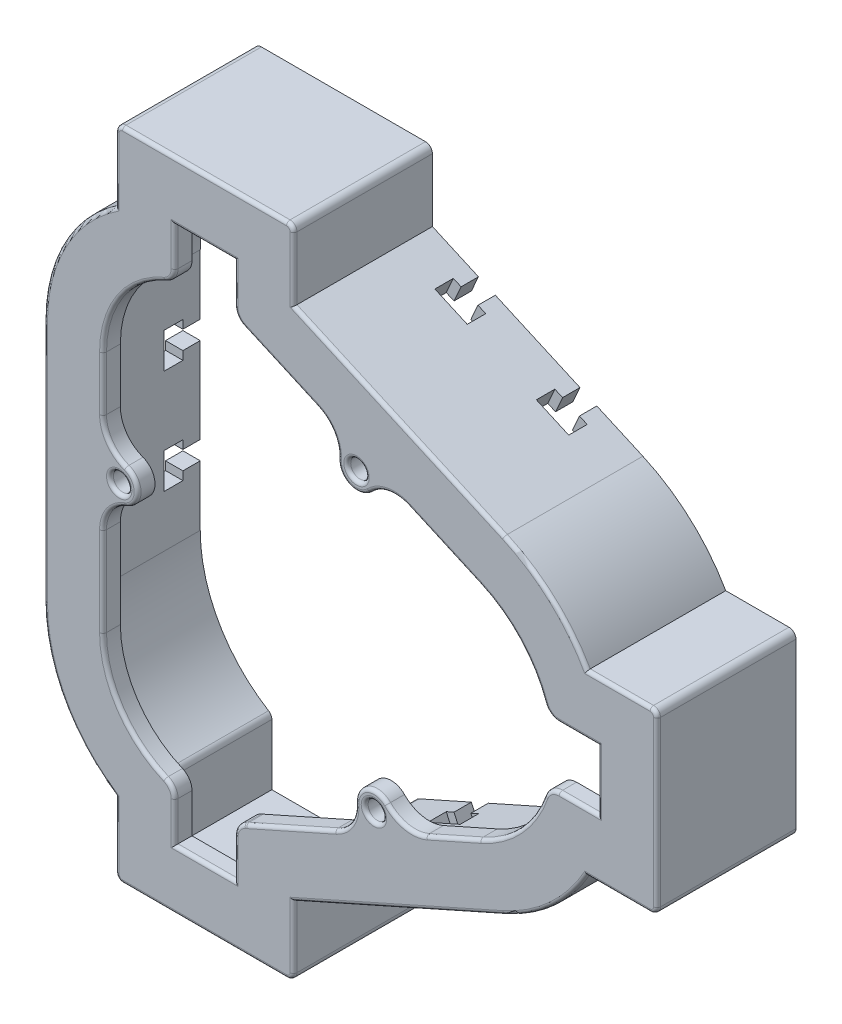
SolidWorks part; units mm, degrees
ref_plane "Front Plane" through (0, 0, 0) normal (0, 0, 1) x (1, 0, 0)
ref_plane "Top Plane" through (0, 0, 0) normal (0, 1, 0) x (1, 0, 0)
ref_plane "Right Plane" through (0, 0, 0) normal (1, 0, 0) x (0, 0, -1)
sketch "Sketch1" plane through (0, 0, -80.01) normal (0, 0, -1) x (-1, 0, 0)
  line L0 (14.1705, 137.7093) -> (22.108, 137.7093) construction
  line L1 (-128.3273, 40.8549) -> (-128.3273, 32.9174) construction
  line L2 (14.1705, -63.937) -> (22.108, -63.937) construction
  line L3 (55.2868, -7.5638) -> (55.2868, 81.3362)
  line L4 (29.093, 120.8247) -> (29.093, 135.1693)
  line L5 (29.093, 135.1693) -> (22.108, 135.1693)
  line L6 (14.1705, 135.1693) -> (22.108, 135.1693)
  line L7 (14.1705, 135.1693) -> (7.1855, 135.1693)
  line L8 (7.1855, 135.1693) -> (7.1855, 120.8247)
  line L9 (3.0278, 115.2711) -> (-82.5915, 77.144)
  line L10 (-111.5749, 47.8399) -> (-125.7873, 47.8399)
  line L11 (-125.7873, 47.8399) -> (-125.7873, 40.8549)
  line L12 (-125.7873, 40.8549) -> (-125.7873, 32.9174)
  line L13 (-125.7873, 32.9174) -> (-125.7873, 25.9324)
  line L14 (-125.7873, 25.9324) -> (-111.5749, 25.9324)
  line L15 (-82.5915, -3.3716) -> (3.0278, -41.4987)
  line L16 (7.1855, -47.0524) -> (7.1855, -61.397)
  line L17 (7.1855, -61.397) -> (14.1705, -61.397)
  line L18 (14.1705, -61.397) -> (22.108, -61.397)
  line L19 (22.108, -61.397) -> (29.093, -61.397)
  line L20 (29.093, -61.397) -> (29.093, -47.0524)
  line L21 (57.8268, -7.5638) -> (57.8268, 81.3362)
  line L22 (31.633, 120.8247) -> (31.633, 137.7093)
  line L23 (31.633, 137.7093) -> (22.108, 137.7093)
  line L24 (22.108, 137.7093) -> (22.108, 117.6323)
  line L25 (14.1705, 117.6323) -> (14.1705, 137.7093)
  line L26 (14.1705, 137.7093) -> (4.6455, 137.7093)
  line L27 (4.6455, 137.7093) -> (4.6455, 120.8247)
  line L28 (1.9945, 117.5914) -> (-83.6248, 79.4643)
  line L29 (-111.5749, 50.3799) -> (-128.3273, 50.3799)
  line L30 (-128.3273, 50.3799) -> (-128.3273, 40.8549)
  line L31 (-128.3273, 40.8549) -> (-106.0032, 40.8549)
  line L32 (-106.0032, 32.9174) -> (-128.3273, 32.9174)
  line L33 (-128.3273, 32.9174) -> (-128.3273, 23.3924)
  line L34 (-128.3273, 23.3924) -> (-111.5749, 23.3924)
  line L35 (-83.6248, -5.692) -> (1.9945, -43.8191)
  line L36 (4.6455, -47.0524) -> (4.6455, -63.937)
  line L37 (4.6455, -63.937) -> (14.1705, -63.937)
  line L38 (14.1705, -63.937) -> (14.1705, -43.86)
  line L39 (22.108, -43.86) -> (22.108, -63.937)
  line L40 (22.108, -63.937) -> (31.633, -63.937)
  line L41 (31.633, -63.937) -> (31.633, -47.0524)
  line L42 (57.8268, -7.5638) -> (57.8268, 81.3362) construction
  line L43 (31.633, 120.8247) -> (31.633, 137.7093) construction
  line L44 (31.633, 137.7093) -> (22.108, 137.7093) construction
  line L47 (14.1705, 137.7093) -> (4.6455, 137.7093) construction
  line L48 (4.6455, 137.7093) -> (4.6455, 120.8247) construction
  line L49 (1.9945, 117.5914) -> (-83.6248, 79.4643) construction
  line L50 (-111.5749, 50.3799) -> (-128.3273, 50.3799) construction
  line L51 (-128.3273, 50.3799) -> (-128.3273, 40.8549) construction
  line L54 (-128.3273, 32.9174) -> (-128.3273, 23.3924) construction
  line L55 (-128.3273, 23.3924) -> (-111.5749, 23.3924) construction
  line L56 (-83.6248, -5.692) -> (1.9945, -43.8191) construction
  line L57 (4.6455, -47.0524) -> (4.6455, -63.937) construction
  line L58 (4.6455, -63.937) -> (14.1705, -63.937) construction
  line L61 (22.108, -63.937) -> (31.633, -63.937) construction
  line L62 (31.633, -63.937) -> (31.633, -47.0524) construction
  line L63 (76.8768, -7.5638) -> (76.8768, 81.3362)
  line L64 (50.683, 130.234) -> (50.683, 156.7593)
  line L65 (50.683, 156.7593) -> (22.108, 156.7593)
  line L66 (14.1705, 156.7593) -> (22.108, 156.7593)
  line L67 (14.1705, 156.7593) -> (-14.4045, 156.7593)
  line L68 (-14.4045, 156.7593) -> (-14.4045, 131.1423)
  line L69 (-14.4045, 131.1423) -> (-91.3743, 96.8669)
  line L70 (-121.6907, 69.4299) -> (-147.3773, 69.4299)
  line L71 (-147.3773, 69.4299) -> (-147.3773, 40.8549)
  line L72 (-147.3773, 40.8549) -> (-147.3773, 32.9174)
  line L73 (-147.3773, 32.9174) -> (-147.3773, 4.3424)
  line L74 (-147.3773, 4.3424) -> (-121.6907, 4.3424)
  line L75 (-91.3743, -23.0945) -> (-14.4045, -57.3699)
  line L76 (-14.4045, -57.3699) -> (-14.4045, -82.987)
  line L77 (-14.4045, -82.987) -> (14.1705, -82.987)
  line L78 (14.1705, -82.987) -> (22.108, -82.987)
  line L79 (22.108, -82.987) -> (50.683, -82.987)
  line L80 (50.683, -82.987) -> (50.683, -56.4617)
  line L81 (70.5268, -7.5638) -> (70.5268, 81.3362)
  line L82 (44.333, 126.7051) -> (44.333, 150.4093)
  line L83 (44.333, 150.4093) -> (22.108, 150.4093)
  line L84 (14.1705, 150.4093) -> (22.108, 150.4093)
  line L85 (14.1705, 150.4093) -> (-8.0545, 150.4093)
  line L86 (-8.0545, 150.4093) -> (-8.0545, 127.0188)
  line L87 (-8.0545, 127.0188) -> (-88.7911, 91.066)
  line L88 (-117.8756, 63.0799) -> (-141.0273, 63.0799)
  line L89 (-141.0273, 63.0799) -> (-141.0273, 40.8549)
  line L90 (-141.0273, 40.8549) -> (-141.0273, 32.9174)
  line L91 (-141.0273, 32.9174) -> (-141.0273, 10.6924)
  line L92 (-141.0273, 10.6924) -> (-117.8756, 10.6924)
  line L93 (-88.7911, -17.2937) -> (-8.0545, -53.2465)
  line L94 (-8.0545, -53.2465) -> (-8.0545, -76.637)
  line L95 (-8.0545, -76.637) -> (14.1705, -76.637)
  line L96 (14.1705, -76.637) -> (22.108, -76.637)
  line L97 (22.108, -76.637) -> (44.333, -76.637)
  line L98 (44.333, -76.637) -> (44.333, -52.9327)
  circle A3 centre (18.1393, 81.3362) radius 19.05 construction
  circle A4 centre (18.1393, -7.5638) radius 47.625 construction
  circle A5 centre (-58.3701, 37.7264) radius 19.05 construction
  arc A6 (-34.0126, 52.4134) -> (-92.9034, 33.8277) centre (-63.458, 43.1205) ccw construction
  arc A7 (-34.0126, 52.4134) -> (-92.9034, 33.8277) centre (-63.458, 43.1205) ccw construction
  arc A8 (-93.857, 33.5267) -> (-33.059, 52.7144) centre (-63.458, 43.1205) ccw construction
  arc A9 (-93.857, 33.5267) -> (-33.059, 52.7144) centre (-63.458, 43.1205) ccw construction
  circle A10 centre (18.1393, 81.3362) radius 36.5125 construction
  circle A11 centre (18.1393, 81.3362) radius 36.5125 construction
  circle A12 centre (49.3813, 43.2476) radius 3.3782
  circle A13 centre (-43.805, -14.1791) radius 3.3782
  circle A14 centre (-37.4305, 90.7903) radius 3.3782
  arc A15 (33.5733, -44.1273) -> (57.8268, -7.5638) centre (18.1393, -7.5638) ccw
  arc A16 (57.8268, 81.3362) -> (33.5733, 117.8997) centre (18.1393, 81.3362) ccw
  arc A17 (31.633, 120.8247) -> (33.5733, 117.8997) centre (34.808, 120.8247) ccw
  arc A18 (14.1705, 117.6323) -> (22.108, 117.6323) centre (18.1393, 81.3362) ccw
  arc A19 (2.7053, 117.8997) -> (4.6455, 120.8247) centre (1.4705, 120.8247) ccw
  arc A20 (2.7053, 117.8997) -> (1.9945, 117.5914) centre (18.1393, 81.3362) ccw
  arc A21 (-83.6248, 79.4643) -> (-108.5831, 52.4919) centre (-64.6643, 36.8862) ccw
  arc A22 (-111.5749, 50.3799) -> (-108.5831, 52.4919) centre (-111.5749, 53.5549) ccw
  arc A23 (-106.0032, 32.9174) -> (-106.0032, 40.8549) centre (-64.6643, 36.8862) ccw
  arc A24 (-108.5831, 21.2805) -> (-111.5749, 23.3924) centre (-111.5749, 20.2174) ccw
  arc A25 (-108.5831, 21.2805) -> (-83.6248, -5.692) centre (-64.6643, 36.8862) ccw
  arc A26 (1.9945, -43.8191) -> (2.7053, -44.1273) centre (18.1393, -7.5638) ccw
  arc A27 (4.6455, -47.0524) -> (2.7053, -44.1273) centre (1.4705, -47.0524) ccw
  arc A28 (22.108, -43.86) -> (14.1705, -43.86) centre (18.1393, -7.5638) ccw
  arc A29 (33.5733, -44.1273) -> (31.633, -47.0524) centre (34.808, -47.0524) ccw
  arc A30 (33.5733, -44.1273) -> (57.8268, -7.5638) centre (18.1393, -7.5638) ccw construction
  arc A31 (57.8268, 81.3362) -> (33.5733, 117.8997) centre (18.1393, 81.3362) ccw construction
  arc A32 (31.633, 120.8247) -> (33.5733, 117.8997) centre (34.808, 120.8247) ccw construction
  arc A34 (2.7053, 117.8997) -> (4.6455, 120.8247) centre (1.4705, 120.8247) ccw construction
  arc A35 (2.7053, 117.8997) -> (1.9945, 117.5914) centre (18.1393, 81.3362) ccw construction
  arc A36 (-83.6248, 79.4643) -> (-108.5831, 52.4919) centre (-64.6643, 36.8862) ccw construction
  arc A37 (-111.5749, 50.3799) -> (-108.5831, 52.4919) centre (-111.5749, 53.5549) ccw construction
  arc A39 (-108.5831, 21.2805) -> (-111.5749, 23.3924) centre (-111.5749, 20.2174) ccw construction
  arc A40 (-108.5831, 21.2805) -> (-83.6248, -5.692) centre (-64.6643, 36.8862) ccw construction
  arc A41 (1.9945, -43.8191) -> (2.7053, -44.1273) centre (18.1393, -7.5638) ccw construction
  arc A42 (4.6455, -47.0524) -> (2.7053, -44.1273) centre (1.4705, -47.0524) ccw construction
  arc A44 (33.5733, -44.1273) -> (31.633, -47.0524) centre (34.808, -47.0524) ccw construction
  arc A45 (-59.2836, 78.0651) -> (-54.2961, 77.1001) centre (-64.6643, 36.8862) ccw construction
  arc A46 (-59.2836, 78.0651) -> (-54.2961, 77.1001) centre (-64.6643, 36.8862) ccw construction
  circle A47 centre (-43.805, -14.1791) radius 6.7564
  circle A48 centre (49.3813, 43.2476) radius 6.7564
  circle A49 centre (-37.4305, 90.7903) radius 6.7564
  arc A50 (32.5855, -41.7872) -> (55.2868, -7.5638) centre (18.1393, -7.5638) ccw
  arc A51 (55.2868, 81.3362) -> (32.5855, 115.5596) centre (18.1393, 81.3362) ccw
  arc A52 (29.093, 120.8247) -> (32.5855, 115.5596) centre (34.808, 120.8247) ccw
  arc A53 (3.693, 115.5596) -> (7.1855, 120.8247) centre (1.4705, 120.8247) ccw
  arc A54 (3.693, 115.5596) -> (3.0278, 115.2711) centre (18.1393, 81.3362) ccw
  arc A55 (-82.5915, 77.144) -> (-106.1897, 51.6414) centre (-64.6643, 36.8862) ccw
  arc A56 (-111.5749, 47.8399) -> (-106.1897, 51.6414) centre (-111.5749, 53.5549) ccw
  arc A57 (-106.1897, 22.1309) -> (-111.5749, 25.9324) centre (-111.5749, 20.2174) ccw
  arc A58 (-106.1897, 22.1309) -> (-82.5915, -3.3716) centre (-64.6643, 36.8862) ccw
  arc A59 (3.0278, -41.4987) -> (3.693, -41.7872) centre (18.1393, -7.5638) ccw
  arc A60 (7.1855, -47.0524) -> (3.693, -41.7872) centre (1.4705, -47.0524) ccw
  arc A61 (32.5855, -41.7872) -> (29.093, -47.0524) centre (34.808, -47.0524) ccw
  arc A62 (50.683, -56.4617) -> (76.8768, -7.5638) centre (18.1393, -7.5638) ccw
  arc A63 (76.8768, 81.3362) -> (50.683, 130.234) centre (18.1393, 81.3362) ccw
  arc A64 (50.683, 130.234) -> (50.683, 130.234) centre (50.683, 130.234) ccw
  arc A65 (-14.4045, 131.1423) -> (-14.4045, 131.1423) centre (-14.4045, 131.1423) ccw
  arc A66 (-14.4045, 131.1423) -> (-14.4045, 131.1423) centre (-14.4045, 131.1423) cw
  arc A67 (-91.3743, 96.8669) -> (-121.6907, 69.4299) centre (-64.6643, 36.8862) ccw
  arc A68 (-121.6907, 69.4299) -> (-121.6907, 69.4299) centre (-121.6907, 69.4299) ccw
  arc A69 (-121.6907, 4.3424) -> (-121.6907, 4.3424) centre (-121.6907, 4.3424) ccw
  arc A70 (-121.6907, 4.3424) -> (-91.3743, -23.0945) centre (-64.6643, 36.8862) ccw
  arc A71 (-14.4045, -57.3699) -> (-14.4045, -57.3699) centre (-14.4045, -57.3699) cw
  arc A72 (-14.4045, -57.3699) -> (-14.4045, -57.3699) centre (-14.4045, -57.3699) ccw
  arc A73 (50.683, -56.4617) -> (50.683, -56.4617) centre (50.683, -56.4617) ccw
  arc A74 (44.333, -52.9327) -> (70.5268, -7.5638) centre (18.1393, -7.5638) ccw
  arc A75 (70.5268, 81.3362) -> (44.333, 126.7051) centre (18.1393, 81.3362) ccw
  arc A76 (44.333, 126.7051) -> (44.333, 126.7051) centre (44.333, 126.7051) ccw
  arc A77 (-8.0545, 127.0188) -> (-8.0545, 127.0188) centre (-8.0545, 127.0188) ccw
  arc A78 (-8.0545, 127.0188) -> (-8.0545, 127.0188) centre (-8.0545, 127.0188) cw
  arc A79 (-88.7911, 91.066) -> (-117.8756, 63.0799) centre (-64.6643, 36.8862) ccw
  arc A80 (-117.8756, 63.0799) -> (-117.8756, 63.0799) centre (-117.8756, 63.0799) ccw
  arc A81 (-117.8756, 10.6924) -> (-117.8756, 10.6924) centre (-117.8756, 10.6924) ccw
  arc A82 (-117.8756, 10.6924) -> (-88.7911, -17.2937) centre (-64.6643, 36.8862) ccw
  arc A83 (-8.0545, -53.2465) -> (-8.0545, -53.2465) centre (-8.0545, -53.2465) cw
  arc A84 (-8.0545, -53.2465) -> (-8.0545, -53.2465) centre (-8.0545, -53.2465) ccw
  arc A85 (44.333, -52.9327) -> (44.333, -52.9327) centre (44.333, -52.9327) ccw
  point P68 (-40.8151, 98.5279)
  arc M83 (33.5733, -44.1273) -> (57.8268, -7.5638) centre (18.1393, -7.5638) ccw
  line M84 (57.8268, -7.5638) -> (57.8268, 81.3362)
  arc M85 (57.8268, 81.3362) -> (33.5733, 117.8997) centre (18.1393, 81.3362) ccw
  arc M86 (33.5733, 117.8997) -> (31.633, 120.8247) centre (34.808, 120.8247) cw
  line M87 (31.633, 120.8247) -> (31.633, 137.7093)
  line M88 (31.633, 137.7093) -> (22.108, 137.7093)
  line M89 (22.108, 137.7093) -> (22.108, 117.6323)
  line M91 (14.1705, 117.6323) -> (14.1705, 137.7093)
  line M92 (14.1705, 137.7093) -> (4.6455, 137.7093)
  line M93 (4.6455, 137.7093) -> (4.6455, 120.8247)
  arc M94 (4.6455, 120.8247) -> (2.7053, 117.8997) centre (1.4705, 120.8247) cw
  arc M95 (2.7053, 117.8997) -> (1.9945, 117.5914) centre (18.1393, 81.3362) ccw
  line M96 (1.9945, 117.5914) -> (-83.6248, 79.4643)
  arc M97 (-83.6248, 79.4643) -> (-108.5831, 52.4919) centre (-64.6643, 36.8862) ccw
  arc M98 (-108.5831, 52.4919) -> (-111.5749, 50.3799) centre (-111.5749, 53.5549) cw
  line M99 (-111.5749, 50.3799) -> (-128.3273, 50.3799)
  line M100 (-128.3273, 50.3799) -> (-128.3273, 40.8549)
  line M101 (-128.3273, 40.8549) -> (-106.0032, 40.8549)
  line M103 (-106.0032, 32.9174) -> (-128.3273, 32.9174)
  line M104 (-128.3273, 32.9174) -> (-128.3273, 23.3924)
  line M105 (-128.3273, 23.3924) -> (-111.5749, 23.3924)
  arc M106 (-111.5749, 23.3924) -> (-108.5831, 21.2805) centre (-111.5749, 20.2174) cw
  arc M107 (-108.5831, 21.2805) -> (-83.6248, -5.692) centre (-64.6643, 36.8862) ccw
  line M108 (-83.6248, -5.692) -> (1.9945, -43.8191)
  arc M109 (1.9945, -43.8191) -> (2.7053, -44.1273) centre (18.1393, -7.5638) ccw
  arc M110 (2.7053, -44.1273) -> (4.6455, -47.0524) centre (1.4705, -47.0524) cw
  line M111 (4.6455, -47.0524) -> (4.6455, -63.937)
  line M112 (4.6455, -63.937) -> (14.1705, -63.937)
  line M113 (14.1705, -63.937) -> (14.1705, -43.86)
  line M115 (22.108, -43.86) -> (22.108, -63.937)
  line M116 (22.108, -63.937) -> (31.633, -63.937)
  line M117 (31.633, -63.937) -> (31.633, -47.0524)
  arc M118 (31.633, -47.0524) -> (33.5733, -44.1273) centre (34.808, -47.0524) cw
  dimension "D2" = 6.7564
  dimension "D3" = 8.4455
  dimension "D4" = 8.4455
  dimension "D5" = 8.4455
  dimension "D6" = 3.3782
  dimension "D1" = 0
  dimension "D7" = 2.54
  dimension "D8" = 19.05
  dimension "D9" = 12.7
extrude "Boss-Extrude1" add sketch "Sketch1" along normal blind 6.35 contours L3 A48 A12 | L9 A49 A14 | L15 A47 A13 | L92 A82 L93 L94 L95 L96 L97 L98 A74 L81 A75 L82 L83 L84 L85 L86 L87 A79 L88 L89 L90 L91 L18 L12 L6 M113 M112 M111 M110 M109 M108 M107 M106 M105 M104 M103 M101 M100 M99 M98 M97 M96 M95 M94 M93 M92 M91 M89 M88 M87 | L16 A60 A59 L15 A47 A58 A57 L14 L13 L17 M103 M104 M105 M106 M107 M108 M109 M110 M111 M112 M113 | A50 A61 L20 L19 L5 L4 A52 A51 L3 A48 M115 M116 M117 M118 M83 M84 M85 M86 M87 M88 M89 | L10 A56 A55 L9 A49 A54 A53 L8 L7 L11 M91 M92 M93 M94 M95 M96 M97 M98 M99 M100 M101 | L74 A70 L75 L76 L77 L78 L79 L80 A62 L63 A63 L64 L65 L66 L67 L68 L69 A67 L70 L71 L72 L73 A82 L92 L91 L90 L89 L88 A79 L87 L86 L85 L84 L83 L82 A75 L81 A74 L98 L97 L96 L95 L94 L93 | L3 A48 | L9 A49 | L15 A47 region at (-57.3347, 16.2007, -80.01) region at (-42.8101, 43.2476, -80.01) region at (-55.6291, 43.2476, -80.01) region at (-12.4476, -62.667, -80.01) region at (-10.678, 136.8923, -80.01) region at (46.3466, -19.8865, -80.01) region at (46.1297, -19.3994, -80.01) region at (32.5874, 95.2231, -80.01) region at (39.972, 96.4976, -80.01) region at (-67.0221, -33.7495, -80.01) region at (-60.8207, -32.2059, -80.01)
extrude "Boss-Extrude2" add sketch "Sketch1<3>" along normal blind 50.8 contours L74 A70 L75 L76 L77 L78 L79 L80 A62 L63 A63 L64 L65 L66 L67 L68 L69 A67 L70 L71 L72 L73 A82 L92 L91 L90 L89 L88 A79 L87 L86 L85 L84 L83 L82 A75 L81 A74 L98 L97 L96 L95 L94 L93 region at (-67.0221, -33.7495, -80.01)
sketch "Sketch1<3>" plane through (0, 0, -80.01) normal (0, 0, -1) x (-1, 0, 0) same geometry as "Sketch1"
sketch "Sketch2" plane through (-76.8768, 0, 0) normal (-1, 0, 0) x (0, 0, 1)
  line L0 (-80.01, 36.8862) -> (-130.81, 36.8862) construction
  line L1 (-130.81, 395.458) -> (-130.81, 402.2144)
  line L2 (-80.01, -7.5638) -> (-80.01, 81.3362) construction
  line L3 (-130.81, -7.5638) -> (-130.81, 81.3362) construction
  line L4 (-130.81, 52.558) -> (-124.46, 52.558)
  line L5 (-124.46, 52.558) -> (-124.46, 49.4592)
  line L6 (-124.46, 49.4592) -> (-117.602, 49.4592)
  line L7 (-117.602, 49.4592) -> (-117.602, 62.4132)
  line L8 (-117.602, 55.9362) -> (-130.81, 55.9362) construction
  line L9 (-124.46, 62.4132) -> (-117.602, 62.4132)
  line L10 (-130.81, 59.3144) -> (-124.46, 59.3144)
  line L11 (-124.46, 59.3144) -> (-124.46, 62.4132)
  line L12 (-130.81, 14.458) -> (-124.46, 14.458)
  line L13 (-124.46, 14.458) -> (-124.46, 11.3592)
  line L14 (-124.46, 11.3592) -> (-117.602, 11.3592)
  line L15 (-117.602, 24.3132) -> (-117.602, 11.3592)
  line L16 (-124.46, 24.3132) -> (-117.602, 24.3132)
  line L17 (-124.46, 21.2144) -> (-124.46, 24.3132)
  line L18 (-130.81, 21.2144) -> (-124.46, 21.2144)
  line L19 (-130.81, 14.458) -> (-130.81, 21.2144)
  line L20 (-130.81, 52.558) -> (-130.81, 59.3144)
  line L21 (-130.81, 402.2144) -> (-124.46, 402.2144)
  line L22 (-124.46, 402.2144) -> (-124.46, 405.3132)
  line L23 (-124.46, 405.3132) -> (-117.602, 405.3132)
  line L24 (-117.602, 405.3132) -> (-117.602, 392.3592)
  line L25 (-124.46, 392.3592) -> (-117.602, 392.3592)
  line L26 (-124.46, 395.458) -> (-124.46, 392.3592)
  line L27 (-130.81, 395.458) -> (-124.46, 395.458)
  line L28 (-130.81, 433.558) -> (-130.81, 440.3144)
  line L29 (-130.81, 440.3144) -> (-124.46, 440.3144)
  line L30 (-124.46, 440.3144) -> (-124.46, 443.4132)
  line L31 (-124.46, 443.4132) -> (-117.602, 443.4132)
  line L32 (-117.602, 430.4592) -> (-117.602, 443.4132)
  line L33 (-124.46, 430.4592) -> (-117.602, 430.4592)
  line L34 (-124.46, 433.558) -> (-124.46, 430.4592)
  line L35 (-130.81, 433.558) -> (-124.46, 433.558)
  dimension "D1" = 6.858
  dimension "D2" = 6.7564
  dimension "D3" = 6.35
  dimension "D4" = 19.05
  dimension "D6" = 6.477
  dimension "D5" = 2
sketch "Sketch3" plane through (51.1185, 114.7931, 0) normal (0.4068, 0.9135, 0) x (0.9135, -0.4068, 0)
  line L0 (1.9385, 130.81) -> (1.9385, 80.01) construction
  line L1 (-40.1897, 130.81) -> (44.0668, 130.81) construction
  line L2 (-40.1897, 80.01) -> (44.0668, 80.01) construction
  line L3 (22.2585, 130.81) -> (22.2585, 117.7036) construction
  line L4 (18.8803, 130.81) -> (18.8803, 124.46)
  line L5 (18.8803, 124.46) -> (15.7815, 124.46)
  line L6 (15.7815, 124.46) -> (15.7815, 117.7036)
  line L7 (15.7815, 117.7036) -> (28.7355, 117.7036)
  line L8 (28.7355, 124.46) -> (28.7355, 117.7036)
  line L9 (25.6367, 124.46) -> (28.7355, 124.46)
  line L10 (25.6367, 130.81) -> (25.6367, 124.46)
  line L11 (-18.3815, 130.81) -> (-18.3815, 117.7036) construction
  line L12 (-21.7597, 130.81) -> (-21.7597, 124.46)
  line L13 (-15.0033, 130.81) -> (-15.0033, 124.46)
  line L14 (-21.7597, 124.46) -> (-24.8585, 124.46)
  line L15 (-24.8585, 124.46) -> (-24.8585, 117.7036)
  line L16 (-15.0033, 124.46) -> (-11.9045, 124.46)
  line L17 (-11.9045, 124.46) -> (-11.9045, 117.7036)
  line L18 (-11.9045, 117.7036) -> (-24.8585, 117.7036)
  line L19 (-21.7597, 130.81) -> (-15.0033, 130.81)
  line L20 (18.8803, 130.81) -> (25.6367, 130.81)
  dimension "D1" = 3.3782
  dimension "D2" = 6.7564
  dimension "D3" = 6.35
  dimension "D4" = 6.477
  dimension "D5" = 20.32
extrude "Cut-Extrude1" cut sketch "Sketch3" against normal blind 18.542
ref_plane "Plane4" through (0, 36.8862, 0) normal (0, 1, 0) x (1, 0, 0)
mirror "Mirror1" about plane through (0, 36.8862, 0) normal (0, 1, 0) of "Cut-Extrude1"
extrude "Cut-Extrude2" cut sketch "Sketch2" against normal blind 18.542
fillet "Fillet1" radius 12.7 6 edges at (49.2059, -18.2386, -83.185) (43.2089, -20.9091, -83.185) (-55.2868, 46.53, -83.185) (-55.2868, 39.9652, -83.185) (42.8316, 94.8495, -83.185) (36.8339, 97.5203, -83.185)
fillet "Fillet2" radius 2.54 16 edges at (141.0273, 63.0799, -108.585) (141.0273, 10.6924, -108.585) (8.0545, 150.4093, -108.585) (-44.333, 150.4093, -108.585) (8.0545, 127.0188, -108.585) (-44.333, 126.7051, -108.585) (8.0545, -53.2465, -108.585) (-44.333, -52.9327, -108.585) (14.4045, -82.987, -105.41) (-50.683, -82.987, -105.41) (-50.683, 156.7593, -105.41) (14.4045, 156.7593, -105.41) (147.3773, 69.4299, -105.41) (147.3773, 4.3424, -105.41) (117.8756, 10.6924, -108.585) (117.8756, 63.0799, -108.585)
fillet "Fillet3" radius 1.27 61 edges at (-49.9391, -82.243, -80.01) (-50.683, -68.4543, -80.01) (-69.9159, -35.2997, -80.01) (-76.8768, 36.8862, -80.01) (-69.9159, 109.072, -80.01) (-50.683, 142.2267, -80.01) (-49.9391, 156.0154, -80.01) (-18.1393, 156.7593, -80.01) (13.6605, 156.0154, -80.01) (14.4045, 142.6808, -80.01) (52.8894, 114.0046, -80.01) (108.7227, 85.5684, -80.01) (133.264, 69.4299, -80.01) (146.6333, 68.686, -80.01) (147.3773, 36.8862, -80.01) (146.6333, 5.0864, -80.01) (133.264, 4.3424, -80.01) (108.7227, -11.7961, -80.01) (52.8894, -40.2322, -80.01) (14.4045, -68.9084, -80.01) (13.6605, -82.243, -80.01) (-18.1393, -82.987, -80.01) (34.0523, 90.7903, -80.01) (-52.7595, 43.2476, -80.01) (40.4268, -14.1791, -80.01) (118.6811, 47.8399, -80.01) (108.279, 48.886, -80.01) (97.0101, 66.8166, -80.01) (69.5395, 82.9562, -80.01) (48.9466, 89.6427, -80.01) (34.682, 84.6182, -80.01) (28.873, 98.5817, -80.01) (10.0751, 109.4362, -80.01) (-3.3597, 115.417, -80.01) (-6.233, 117.6657, -80.01) (-7.1855, 127.997, -80.01) (-18.1393, 135.1693, -80.01) (-29.093, 127.997, -80.01) (-30.0455, 117.6657, -80.01) (-49.0955, 101.8702, -80.01) (-55.2868, 71.4076, -80.01) (-53.0179, 54.2346, -80.01) (-42.6249, 43.2476, -80.01) (-53.0179, 32.2606, -80.01) (-55.2868, 8.7262, -80.01) (-49.0955, -28.0979, -80.01) (-30.0455, -43.8933, -80.01) (-29.093, -54.2247, -80.01) (-18.1393, -61.397, -80.01) (-7.1855, -54.2247, -80.01) (-6.233, -43.8933, -80.01) (-3.3597, -41.6446, -80.01) (13.2624, -34.2446, -80.01) (35.2476, -21.9706, -80.01) (41.0565, -8.007, -80.01) (55.3212, -13.0317, -80.01) (72.7268, -7.7645, -80.01) (97.0101, 6.9558, -80.01) (108.279, 24.8863, -80.01) (118.6811, 25.9324, -80.01) (125.7873, 36.8862, -80.01)
equation "\"D4@Sketch1\"=\"D3@Sketch1\""
equation "\"D5@Sketch1\"=\"D3@Sketch1\""
